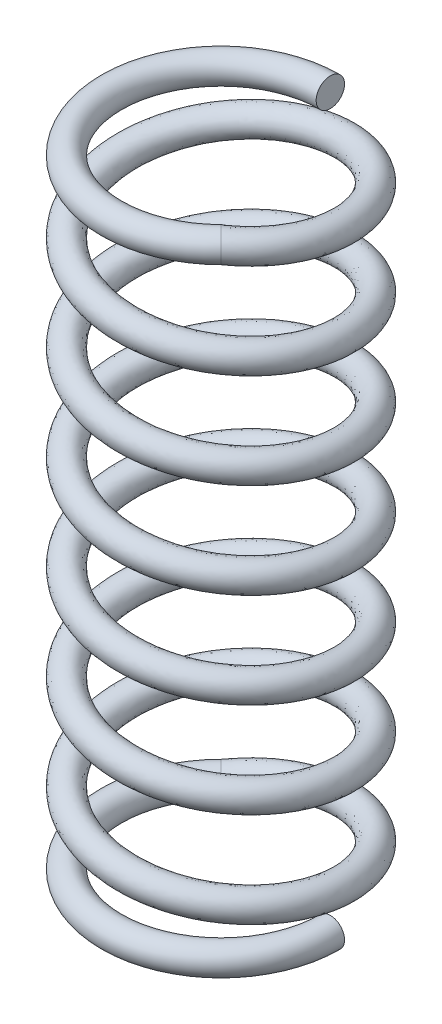
SolidWorks part; units mm, degrees
note: '?' marks a value the reader was unsure of.
ref_plane "Front Plane" through (0, 0, 0) normal (0, 0, 1) x (1, 0, 0)
ref_plane "Top Plane" through (0, 0, 0) normal (0, 1, 0) x (1, 0, 0)
ref_plane "Right Plane" through (0, 0, 0) normal (1, 0, 0) x (0, 0, -1)
sketch "Sketch1" plane through (0, 0, 0) normal (0, 1, 0) x (1, 0, 0)
  circle A0 centre (0, 0) radius 5
  dimension "D1" = 10
curve "Helix/Spiral1" pitch 3.8462 height 25 turns 6.5
sketch "Sketch2" plane through (0, 0, 0) normal (1, 0, 0) x (0, 0, -1)
  circle A0 centre (4.425, 0.2456) radius 0.575
  dimension "D1" = 1.15
  dimension "D2" = 4.425
sweep "Sweep2" add profiles "Sketch2" path "Helix/Spiral1"
ref_point "Point1"
ref_axis "Axis1" through (3.1289, 24.7648, 3.1289) along (-0.7071, 0, 0.7071)?
ref_point "Point2"
ref_axis "Axis2" through (-3.1289, -0.2352, -3.1289) along (-0.7071, 0, 0.7071)?
ref_plane "Plane1" through (0, -0.2352, 0) normal (0, 1, 0) x (1, 0, 0)
ref_axis "Axis3" through (0, 26.7317, 0) along (0, -1, 0)?
ref_plane "Plane2" through (0, 24.7648, 0) normal (0, 1, 0) x (1, 0, 0)
sketch "Sketch5" plane through (0, 24.7648, 0) normal (0, 1, 0) x (1, 0, 0)
  line L1 (2.7224, -2.7224) -> (3.5355, -3.5355) construction
  arc A0 (0, 4.425) -> (3.1289, -3.1289) centre (0, 0) ccw
sketch "Sketch6" plane through (0, 0, 0) normal (-0.7071, 0, 0.7071) x (0.7071, 0, 0.7071)
  circle A0 centre (4.425, 24.7648) radius 0.575
sweep "Sweep3" add profiles "Sketch6" path "Sketch5"
sketch "Sketch7" plane through (0, -0.2352, 0) normal (0, 1, 0) x (1, 0, 0)
  arc A0 (-3.1289, 3.1289) -> (4.425, 0) centre (0, 0) ccw
sketch "Sketch8" plane through (0, 0, 0) normal (-0.7071, 0, 0.7071) x (0.7071, 0, 0.7071)
  circle A0 centre (-4.425, -0.2352) radius 0.575 construction
  circle A1 centre (-4.425, -0.2352) radius 0.575
sweep "Sweep4" add profiles "Sketch8" path "Sketch7"
ref_plane "Plane3" through (0, -0.575, 0) normal (0, 1, 0) x (1, 0, 0)
ref_plane "Plane4" through (0, 25.3398, 0) normal (0, 1, 0) x (1, 0, 0)
